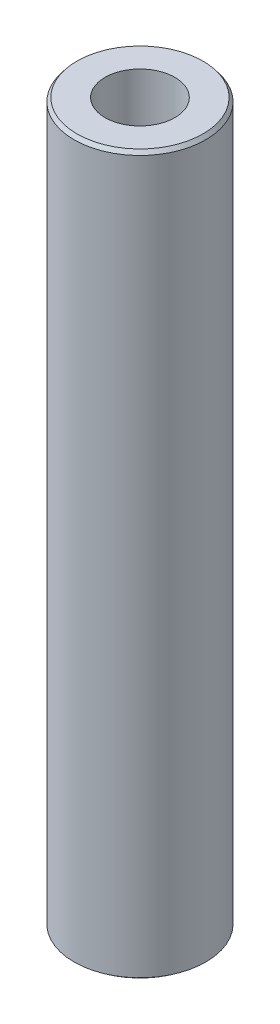
SolidWorks part; units mm, degrees
ref_plane "Front Plane" through (0, 0, 0) normal (0, 0, 1) x (1, 0, 0)
ref_plane "Top Plane" through (0, 0, 0) normal (0, 1, 0) x (1, 0, 0)
ref_plane "Right Plane" through (0, 0, 0) normal (1, 0, 0) x (0, 0, -1)
sketch "Sketch1" plane through (0, 0, 0) normal (0, 1, 0) x (1, 0, 0)
  circle A0 centre (0, 0) radius 55
  dimension "SHAFT_OD" = 110
extrude "Boss-Extrude1" add sketch "Sketch1" along normal blind 600
sketch "Sketch2" plane through (0, 0, 0) normal (0, 1, 0) x (1, 0, 0)
  circle A0 centre (0, 0) radius 29.165
  dimension "BORE_D" = 58.3299
extrude "Cut-Extrude1" cut sketch "Sketch2" along normal through all
chamfer "Chamfer1" distance 3.0698 angle 37.338 2 edges at (0, 600, 55) (0, 0, 55) first distance on face at (0, 600, 55) first distance on face at (0, 0, 29.165)
